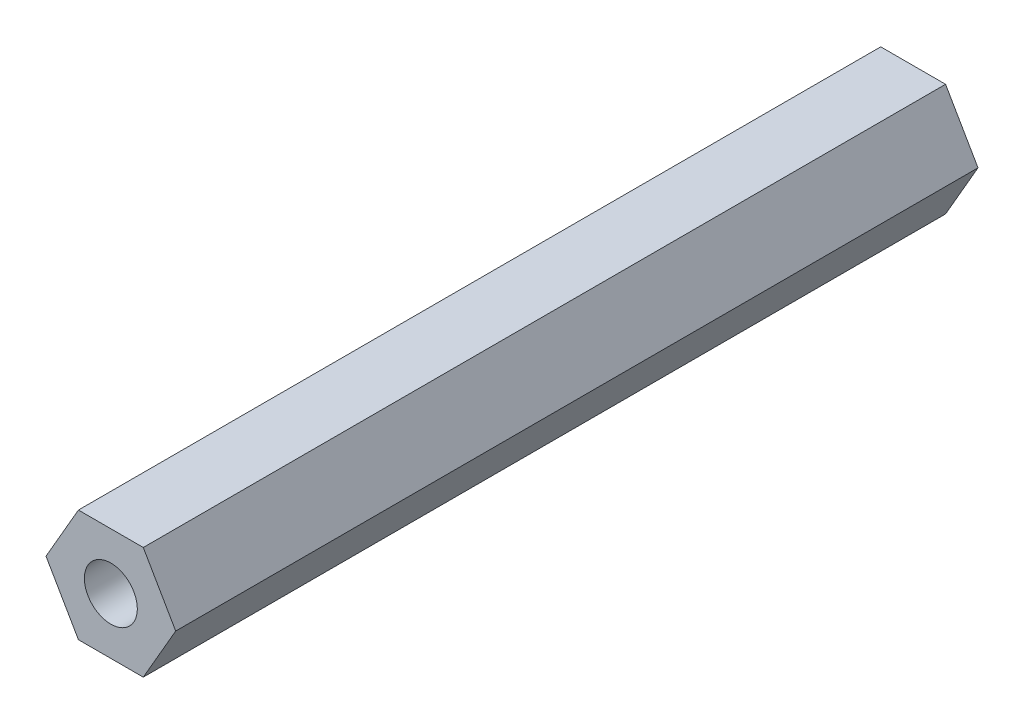
SolidWorks part; units mm, degrees
ref_plane "Front" through (0, 0, 0) normal (0, 0, 1) x (1, 0, 0)
ref_plane "Top" through (0, 0, 0) normal (0, 1, 0) x (1, 0, 0)
ref_plane "Right" through (0, 0, 0) normal (1, 0, 0) x (0, 0, -1)
sketch "Esquisse1" plane through (0, 0, 0) normal (0, 0, 1) x (1, 0, 0)
  line L1 (4.0415, 0) -> (2.0207, 3.5)
  line L2 (2.0207, 3.5) -> (-2.0207, 3.5)
  line L3 (-2.0207, 3.5) -> (-4.0415, 0)
  line L4 (-4.0415, 0) -> (-2.0207, -3.5)
  line L5 (-2.0207, -3.5) -> (2.0207, -3.5)
  line L6 (2.0207, -3.5) -> (4.0415, 0)
  circle A0 centre (0, 0) radius 3.5 construction
  dimension "D1" = 7
extrude "Boss.-Extru.1" add sketch "Esquisse1" along normal blind 50
sketch "Esquisse2" plane through (0, 0, 50) normal (0, 0, 1) x (1, 0, 0)
  circle A0 centre (0, 0) radius 1.65
  dimension "D1" = 3.3
extrude "Enlèv. mat.-Extru.1" cut sketch "Esquisse2" against normal blind 9
extrude "Enlèv. mat.-Extru.2" cut sketch "Esquisse2<2>" along normal blind 9 from vertex starting at point (2.0207, 3.5, 0)
sketch "Esquisse2<2>" plane through (0, 0, 50) normal (0, 0, 1) x (1, 0, 0) same geometry as "Esquisse2"
